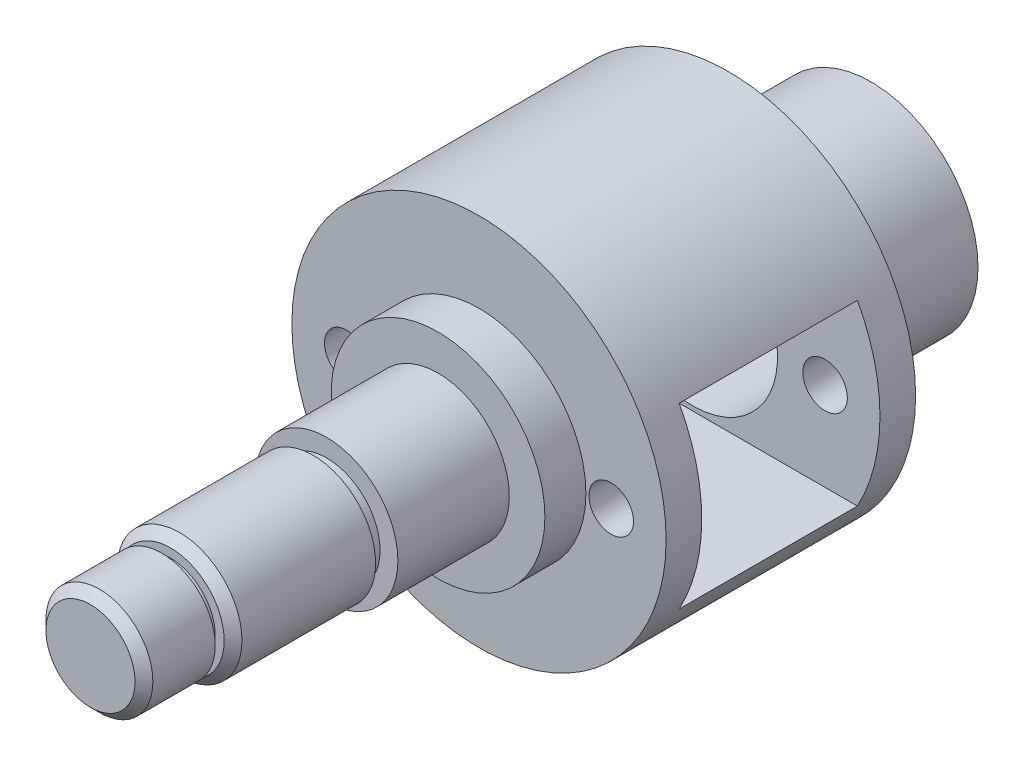
SolidWorks part; units mm, degrees
ref_plane "Plan de face" through (0, 0, 0) normal (0, 0, 1) x (1, 0, 0)
ref_plane "Plan de dessus" through (0, 0, 0) normal (0, 1, 0) x (1, 0, 0)
ref_plane "Plan de droite" through (0, 0, 0) normal (1, 0, 0) x (0, 0, -1)
sketch "Esquisse1" plane through (0, 0, 0) normal (0, 0, 1) x (1, 0, 0)
  circle A0 centre (0, 0) radius 6
  dimension "D1" = 12
extrude "Boss.-Extru.1" add sketch "Esquisse1" along normal blind 8
sketch "Esquisse2" plane through (0, 0, 8) normal (0, 0, 1) x (1, 0, 0)
  circle A0 centre (0, 0) radius 10.5
  circle A1 centre (-7.4186, -0.0266) radius 1.25
  circle A2 centre (7.4186, -0.0266) radius 1.25
  dimension "D1" = 21
  dimension "D2" = 2.5
  dimension "D3" = 2.5
extrude "Boss.-Extru.2" add sketch "Esquisse2" along normal blind 14
sketch "Esquisse3" plane through (0, 0, 22) normal (0, 0, 1) x (1, 0, 0)
  circle A0 centre (0, 0) radius 6
  dimension "D1" = 12
extrude "Boss.-Extru.3" add sketch "Esquisse3" along normal blind 2.3
sketch "Esquisse4" plane through (0, 0, 24.3) normal (0, 0, 1) x (1, 0, 0)
  circle A0 centre (0, 0) radius 4
  dimension "D1" = 8
extrude "Boss.-Extru.4" add sketch "Esquisse4" along normal blind 6.25
sketch "Esquisse5" plane through (0, 0, 30.55) normal (0, 0, 1) x (1, 0, 0)
  circle A0 centre (0, 0) radius 3
  dimension "D1" = 6
extrude "Boss.-Extru.5" add sketch "Esquisse5" along normal blind 0.75
sketch "Esquisse7" plane through (0, 0, 31.3) normal (0, 0, 1) x (1, 0, 0)
  circle A0 centre (0, 0) radius 3.5
  dimension "D1" = 7
extrude "Boss.-Extru.6" add sketch "Esquisse7" along normal blind 8
sketch "Esquisse8" plane through (0, 0, 39.3) normal (0, 0, 1) x (1, 0, 0)
  circle A0 centre (0, 0) radius 2.5
  dimension "D1" = 5
extrude "Boss.-Extru.7" add sketch "Esquisse8" along normal blind 0.5
sketch "Esquisse9" plane through (0, 0, 39.8) normal (0, 0, 1) x (1, 0, 0)
  circle A0 centre (0, 0) radius 3
  dimension "D1" = 6
extrude "Boss.-Extru.8" add sketch "Esquisse9" along normal blind 4
sketch "Esquisse10" plane through (0, 0, 0) normal (0, 0, -1) x (-1, 0, 0)
  circle A0 centre (0, 0) radius 4.75
  dimension "D1" = 9.5
extrude "Enlèv. mat.-Extru.1" cut sketch "Esquisse10" against normal blind 21
chamfer "Chanfrein1" distance 0.5 angle 45 1 edges at (3.5, 0, 39.3)
chamfer "Chanfrein2" distance 0.5 angle 45 1 edges at (3, 0, 43.8)
sketch "Sketch1" plane through (0, 0, 0) normal (1, 0, 0) x (0, 0, -1)
  line L0 (-10, 0) -> (0, 0) construction
  line L1 (-20, 5) -> (-10, 5)
  line L2 (-20, 5) -> (-20, -5)
  line L3 (-20, -5) -> (-10, -5)
  line L4 (-10, 5) -> (-10, -5)
  dimension "D1" = 10
  dimension "D2" = 10
  dimension "D3" = 10
extrude "Cut-Extrude1" cut sketch "Sketch1" against normal blind 12 and the other way blind 12
